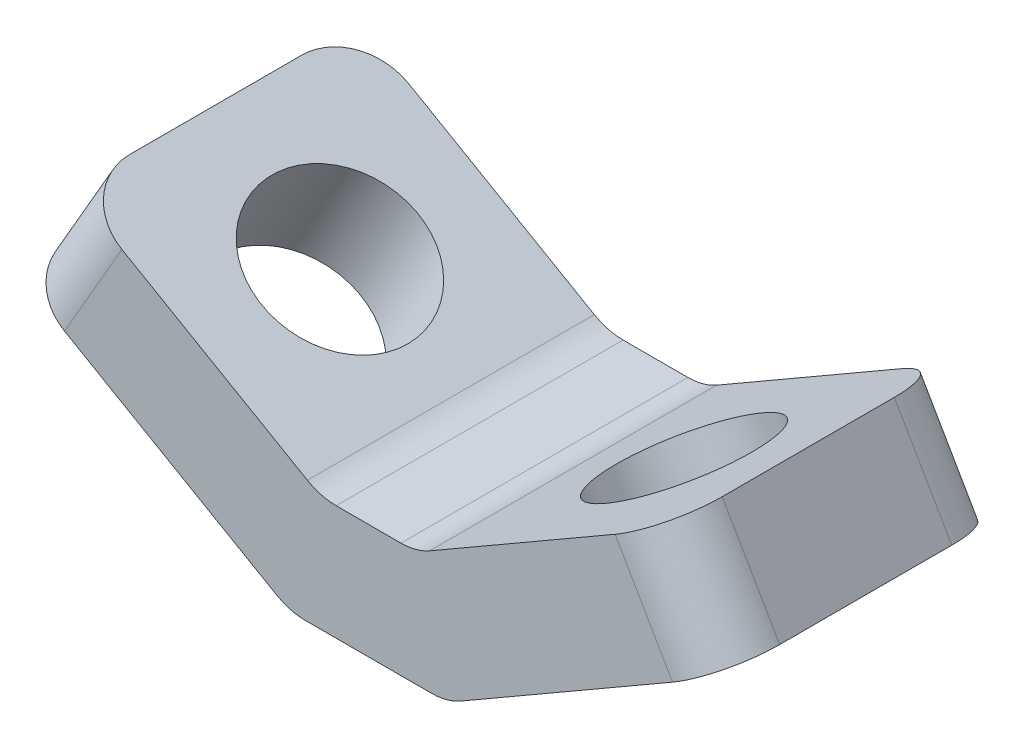
SolidWorks part; units mm, degrees
ref_plane "正面" through (0, 0, 0) normal (0, 0, 1) x (1, 0, 0)
ref_plane "平面" through (0, 0, 0) normal (0, 1, 0) x (1, 0, 0)
ref_plane "右側面" through (0, 0, 0) normal (1, 0, 0) x (0, 0, -1)
sketch "ｽｹｯﾁ1" plane through (0, 0, 0) normal (0, 0, 1) x (1, 0, 0)
  line L0 (0, 0) -> (-14.3827, 8.3038)
  line L1 (-14.3827, 8.3038) -> (-11.3827, 13.5)
  line L2 (-11.3827, 13.5) -> (1.6077, 6)
  line L3 (1.6077, 6) -> (6.6077, 6)
  line L4 (6.6077, 6) -> (19.5981, 13.5)
  line L5 (19.5981, 13.5) -> (22.5981, 8.3038)
  line L6 (22.5981, 8.3038) -> (8.2154, 0)
  line L7 (8.2154, 0) -> (0, 0)
  dimension "D1" = 150
  dimension "D2" = 150
  dimension "D3" = 6
  dimension "D4" = 6
  dimension "D5" = 6
  dimension "D6" = 15
  dimension "D7" = 15
  dimension "D8" = 5
extrude "ﾎﾞｽ - 押し出し1" add sketch "ｽｹｯﾁ1" along normal mid plane 15
sketch "ｽｹｯﾁ2" plane through (0, 0, 0) normal (-0.5, -0.866, 0) x (0, 0, 1)
  line L0 (7.5, 1.6077) -> (7.5, 16.6077) construction
  circle A0 centre (0, 9.1077) radius 4.1
  point P6 (7.5, 9.1077)
  dimension "D1" = 8.2
extrude "ｶｯﾄ - 押し出し1" cut sketch "ｽｹｯﾁ2" against normal through all both and the other way through all
sketch "ｽｹｯﾁ3" plane through (2.0538, -3.5574, 0) normal (0.5, -0.866, 0) x (0, 0, -1)
  line L0 (-7.5, 23.7224) -> (-7.5, 8.7224) construction
  line L1 (-7.5, 23.7224) -> (7.5, 23.7224) construction
  circle A0 centre (0, 16.2224) radius 4.1
  point P4 (-7.5, 16.2224)
  point P7 (0, 23.7224)
  dimension "D1" = 8.2
extrude "ｶｯﾄ - 押し出し2" cut sketch "ｽｹｯﾁ3" against normal through all both and the other way through all
fillet "ﾌｨﾚｯﾄ1" radius 3 8 edges at (21.0981, 10.9019, -7.5) (21.0981, 10.9019, 7.5) (-12.8827, 10.9019, -7.5) (-12.8827, 10.9019, 7.5) (8.2154, 0, 0) (0, 0, 0) (6.6077, 6, 0) (1.6077, 6, 0)
equation "\"D4@ｽｹｯﾁ1\"=\"D3@ｽｹｯﾁ1\""
equation "\"D5@ｽｹｯﾁ1\"=\"D3@ｽｹｯﾁ1\""
equation "\"D2@ｽｹｯﾁ1\"=\"D1@ｽｹｯﾁ1\""
